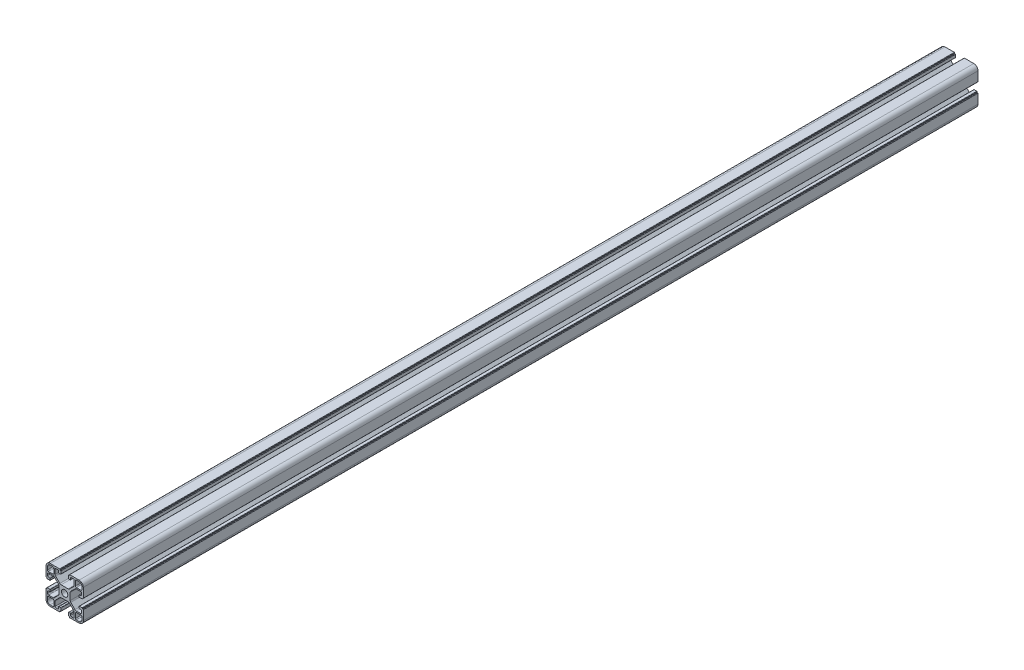
SolidWorks part; units mm, degrees
note: '?' marks a value the reader was unsure of.
material "6063-T5"
ref_plane "前视基准面" through (0, 0, 0) normal (0, 0, 1) x (1, 0, 0)
ref_plane "上视基准面" through (0, 0, 0) normal (0, 1, 0) x (1, 0, 0)
ref_plane "右视基准面" through (0, 0, 0) normal (1, 0, 0) x (0, 0, -1)
sketch "草图1" plane through (0, 0, 0) normal (0, 0, 1) x (1, 0, 0)
  line L0 (5.1, -19.2) -> (5.1, -19.7)
  line L1 (4.4, -19) -> (4.9, -19)
  line L2 (5.4, -20) -> (15.5, -20)
  line L3 (4.1, -15.8) -> (4.1, -18.8)
  line L4 (20, -15.5) -> (20, -5.4)
  line L5 (6.1, -15.5) -> (4.4, -15.5)
  line L6 (19.7, -5.1) -> (19.2, -5.1)
  line L7 (6.4, -17.2) -> (6.4, -15.8)
  line L8 (19, -4.9) -> (19, -4.4)
  line L9 (9.25, -18.2) -> (7.4, -18.2)
  line L10 (18.7, -4.1) -> (15.8, -4.1)
  line L11 (10.25, -12.4926) -> (10.25, -17.2)
  line L12 (15.5, -4.4) -> (15.5, -6.1)
  line L13 (5.1716, -6.5858) -> (9.6642, -11.0784)
  line L14 (15.8, -6.4) -> (17.2, -6.4)
  line L15 (-3.7574, -6) -> (3.7574, -6)
  line L16 (18.2, -7.4) -> (18.2, -9.25)
  line L17 (-9.6642, -11.0784) -> (-5.1716, -6.5858)
  line L18 (17.2, -10.25) -> (12.4926, -10.25)
  line L19 (-10.25, -17.2) -> (-10.25, -12.4926)
  line L20 (11.0784, -9.6642) -> (6.5858, -5.1716)
  line L21 (-7.4, -18.2) -> (-9.25, -18.2)
  line L22 (6, -3.7574) -> (6, 3.7574)
  line L23 (-6.4, -15.8) -> (-6.4, -17.2)
  line L24 (6.5858, 5.1716) -> (11.0784, 9.6642)
  line L25 (-4.4, -15.5) -> (-6.1, -15.5)
  line L26 (12.4926, 10.25) -> (17.2, 10.25)
  line L27 (-4.1, -18.8) -> (-4.1, -15.8)
  line L28 (18.2, 9.25) -> (18.2, 7.4)
  line L29 (-4.9, -19) -> (-4.4, -19)
  line L30 (17.2, 6.4) -> (15.8, 6.4)
  line L31 (-5.1, -19.7) -> (-5.1, -19.2)
  line L32 (15.5, 6.1) -> (15.5, 4.4)
  line L33 (-15.5, -20) -> (-5.4, -20)
  line L34 (15.8, 4.1) -> (18.7, 4.1)
  line L35 (-20, -5.4) -> (-20, -15.5)
  line L36 (19, 4.4) -> (19, 4.9)
  line L37 (-19.2, -5.1) -> (-19.7, -5.1)
  line L38 (19.2, 5.1) -> (19.7, 5.1)
  line L39 (-19, -4.4) -> (-19, -4.9)
  line L40 (20, 5.4) -> (20, 15.5)
  line L41 (-15.8, -4.1) -> (-18.7, -4.1)
  line L42 (15.5, 20) -> (5.4, 20)
  line L43 (-15.5, -6.1) -> (-15.5, -4.4)
  line L44 (5.1, 19.7) -> (5.1, 19.2)
  line L45 (-17.2, -6.4) -> (-15.8, -6.4)
  line L46 (4.9, 19) -> (4.4, 19)
  line L47 (-18.2, -9.25) -> (-18.2, -7.4)
  line L48 (4.1, 18.7) -> (4.1, 15.8)
  line L49 (-12.4926, -10.25) -> (-17.2, -10.25)
  line L50 (4.4, 15.5) -> (6.1, 15.5)
  line L51 (-6.5858, -5.1716) -> (-11.0784, -9.6642)
  line L52 (6.4, 15.8) -> (6.4, 17.2)
  line L53 (-6, 3.7574) -> (-6, -3.7574)
  line L54 (7.4, 18.2) -> (9.25, 18.2)
  line L55 (-11.0784, 9.6642) -> (-6.5858, 5.1716)
  line L56 (10.25, 17.2) -> (10.25, 12.4926)
  line L57 (-17.2, 10.25) -> (-12.4926, 10.25)
  line L58 (9.6642, 11.0784) -> (5.1716, 6.5858)
  line L59 (-18.2, 7.4) -> (-18.2, 9.25)
  line L60 (3.7574, 6) -> (-3.7574, 6)
  line L61 (-15.8, 6.4) -> (-17.2, 6.4)
  line L62 (-5.1716, 6.5858) -> (-9.6642, 11.0784)
  line L63 (-15.5, 4.4) -> (-15.5, 6.1)
  line L64 (-10.25, 12.4926) -> (-10.25, 17.2)
  line L65 (-18.7, 4.1) -> (-15.8, 4.1)
  line L66 (-9.25, 18.2) -> (-7.4, 18.2)
  line L67 (-19, 4.9) -> (-19, 4.4)
  line L68 (-6.4, 17.2) -> (-6.4, 15.8)
  line L69 (-19.7, 5.1) -> (-19.2, 5.1)
  line L70 (-6.1, 15.5) -> (-4.4, 15.5)
  line L71 (-20, 15.5) -> (-20, 5.4)
  line L72 (-4.1, 15.8) -> (-4.1, 18.7)
  line L73 (-5.4, 20) -> (-15.5, 20)
  line L74 (-4.4, 19) -> (-4.9, 19)
  line L75 (-5.1, 19.2) -> (-5.1, 19.7)
  line L76 (12.55, 18.5) -> (15.5, 18.5)
  line L77 (11.55, 12.55) -> (11.55, 17.5)
  line L78 (18.5, 15.5) -> (18.5, 12.55)
  line L79 (17.5, 11.55) -> (12.55, 11.55)
  line L80 (-11.55, 17.5) -> (-11.55, 12.55)
  line L81 (-15.5, 18.5) -> (-12.55, 18.5)
  line L82 (-12.55, 11.55) -> (-17.5, 11.55)
  line L83 (-18.5, 12.55) -> (-18.5, 15.5)
  line L84 (-12.55, -18.5) -> (-15.5, -18.5)
  line L85 (-11.55, -12.55) -> (-11.55, -17.5)
  line L86 (-18.5, -15.5) -> (-18.5, -12.55)
  line L87 (-17.5, -11.55) -> (-12.55, -11.55)
  line L88 (11.55, -17.5) -> (11.55, -12.55)
  line L89 (15.5, -18.5) -> (12.55, -18.5)
  line L90 (12.55, -11.55) -> (17.5, -11.55)
  line L91 (18.5, -12.55) -> (18.5, -15.5)
  arc A0 (5.1, -19.2) -> (4.9, -19) centre (4.9, -19.2) ccw
  arc A1 (5.1, -19.7) -> (5.4, -20) centre (5.4, -19.7) ccw
  arc A2 (4.1, -18.8) -> (4.4, -19) centre (4.3282, -18.7827) ccw
  arc A3 (15.5, -20) -> (20, -15.5) centre (15.5, -15.5) ccw
  arc A4 (4.4, -15.5) -> (4.1, -15.8) centre (4.4, -15.8) ccw
  arc A5 (20, -5.4) -> (19.7, -5.1) centre (19.7, -5.4) ccw
  arc A6 (6.4, -15.8) -> (6.1, -15.5) centre (6.1, -15.8) ccw
  arc A7 (19, -4.9) -> (19.2, -5.1) centre (19.2, -4.9) ccw
  arc A8 (6.4, -17.2) -> (7.4, -18.2) centre (7.4, -17.2) ccw
  arc A9 (19, -4.4) -> (18.7, -4.1) centre (18.7, -4.4) ccw
  arc A10 (9.25, -18.2) -> (10.25, -17.2) centre (9.25, -17.2) ccw
  arc A11 (15.8, -4.1) -> (15.5, -4.4) centre (15.8, -4.4) ccw
  arc A12 (10.25, -12.4926) -> (9.6642, -11.0784) centre (8.25, -12.4926) ccw
  arc A13 (15.5, -6.1) -> (15.8, -6.4) centre (15.8, -6.1) ccw
  arc A14 (5.1716, -6.5858) -> (3.7574, -6) centre (3.7574, -8) ccw
  arc A15 (18.2, -7.4) -> (17.2, -6.4) centre (17.2, -7.4) ccw
  arc A16 (-3.7574, -6) -> (-5.1716, -6.5858) centre (-3.7574, -8) ccw
  arc A17 (17.2, -10.25) -> (18.2, -9.25) centre (17.2, -9.25) ccw
  arc A18 (-9.6642, -11.0784) -> (-10.25, -12.4926) centre (-8.25, -12.4926) ccw
  arc A19 (11.0784, -9.6642) -> (12.4926, -10.25) centre (12.4926, -8.25) ccw
  arc A20 (-10.25, -17.2) -> (-9.25, -18.2) centre (-9.25, -17.2) ccw
  arc A21 (6, -3.7574) -> (6.5858, -5.1716) centre (8, -3.7574) ccw
  arc A22 (-7.4, -18.2) -> (-6.4, -17.2) centre (-7.4, -17.2) ccw
  arc A23 (6.5858, 5.1716) -> (6, 3.7574) centre (8, 3.7574) ccw
  arc A24 (-6.1, -15.5) -> (-6.4, -15.8) centre (-6.1, -15.8) ccw
  arc A25 (12.4926, 10.25) -> (11.0784, 9.6642) centre (12.4926, 8.25) ccw
  arc A26 (-4.1, -15.8) -> (-4.4, -15.5) centre (-4.4, -15.8) ccw
  arc A27 (18.2, 9.25) -> (17.2, 10.25) centre (17.2, 9.25) ccw
  arc A28 (-4.4, -19) -> (-4.1, -18.8) centre (-4.3282, -18.7827) ccw
  arc A29 (17.2, 6.4) -> (18.2, 7.4) centre (17.2, 7.4) ccw
  arc A30 (-4.9, -19) -> (-5.1, -19.2) centre (-4.9, -19.2) ccw
  arc A31 (15.8, 6.4) -> (15.5, 6.1) centre (15.8, 6.1) ccw
  arc A32 (-5.4, -20) -> (-5.1, -19.7) centre (-5.4, -19.7) ccw
  arc A33 (15.5, 4.4) -> (15.8, 4.1) centre (15.8, 4.4) ccw
  arc A34 (-20, -15.5) -> (-15.5, -20) centre (-15.5, -15.5) ccw
  arc A35 (18.7, 4.1) -> (19, 4.4) centre (18.7, 4.4) ccw
  arc A36 (-19.7, -5.1) -> (-20, -5.4) centre (-19.7, -5.4) ccw
  arc A37 (19.2, 5.1) -> (19, 4.9) centre (19.2, 4.9) ccw
  arc A38 (-19.2, -5.1) -> (-19, -4.9) centre (-19.2, -4.9) ccw
  arc A39 (19.7, 5.1) -> (20, 5.4) centre (19.7, 5.4) ccw
  arc A40 (-18.7, -4.1) -> (-19, -4.4) centre (-18.7, -4.4) ccw
  arc A41 (20, 15.5) -> (15.5, 20) centre (15.5, 15.5) ccw
  arc A42 (-15.5, -4.4) -> (-15.8, -4.1) centre (-15.8, -4.4) ccw
  arc A43 (5.4, 20) -> (5.1, 19.7) centre (5.4, 19.7) ccw
  arc A44 (-15.8, -6.4) -> (-15.5, -6.1) centre (-15.8, -6.1) ccw
  arc A45 (4.9, 19) -> (5.1, 19.2) centre (4.9, 19.2) ccw
  arc A46 (-17.2, -6.4) -> (-18.2, -7.4) centre (-17.2, -7.4) ccw
  arc A47 (4.4, 19) -> (4.1, 18.7) centre (4.4, 18.7) ccw
  arc A48 (-18.2, -9.25) -> (-17.2, -10.25) centre (-17.2, -9.25) ccw
  arc A49 (4.1, 15.8) -> (4.4, 15.5) centre (4.4, 15.8) ccw
  arc A50 (-12.4926, -10.25) -> (-11.0784, -9.6642) centre (-12.4926, -8.25) ccw
  arc A51 (6.1, 15.5) -> (6.4, 15.8) centre (6.1, 15.8) ccw
  arc A52 (-6.5858, -5.1716) -> (-6, -3.7574) centre (-8, -3.7574) ccw
  arc A53 (7.4, 18.2) -> (6.4, 17.2) centre (7.4, 17.2) ccw
  arc A54 (-6, 3.7574) -> (-6.5858, 5.1716) centre (-8, 3.7574) ccw
  arc A55 (10.25, 17.2) -> (9.25, 18.2) centre (9.25, 17.2) ccw
  arc A56 (-11.0784, 9.6642) -> (-12.4926, 10.25) centre (-12.4926, 8.25) ccw
  arc A57 (9.6642, 11.0784) -> (10.25, 12.4926) centre (8.25, 12.4926) ccw
  arc A58 (-17.2, 10.25) -> (-18.2, 9.25) centre (-17.2, 9.25) ccw
  arc A59 (3.7574, 6) -> (5.1716, 6.5858) centre (3.7574, 8) ccw
  arc A60 (-18.2, 7.4) -> (-17.2, 6.4) centre (-17.2, 7.4) ccw
  arc A61 (-5.1716, 6.5858) -> (-3.7574, 6) centre (-3.7574, 8) ccw
  arc A62 (-15.5, 6.1) -> (-15.8, 6.4) centre (-15.8, 6.1) ccw
  arc A63 (-10.25, 12.4926) -> (-9.6642, 11.0784) centre (-8.25, 12.4926) ccw
  arc A64 (-15.8, 4.1) -> (-15.5, 4.4) centre (-15.8, 4.4) ccw
  arc A65 (-9.25, 18.2) -> (-10.25, 17.2) centre (-9.25, 17.2) ccw
  arc A66 (-19, 4.4) -> (-18.7, 4.1) centre (-18.7, 4.4) ccw
  arc A67 (-6.4, 17.2) -> (-7.4, 18.2) centre (-7.4, 17.2) ccw
  arc A68 (-19, 4.9) -> (-19.2, 5.1) centre (-19.2, 4.9) ccw
  arc A69 (-6.4, 15.8) -> (-6.1, 15.5) centre (-6.1, 15.8) ccw
  arc A70 (-20, 5.4) -> (-19.7, 5.1) centre (-19.7, 5.4) ccw
  arc A71 (-4.4, 15.5) -> (-4.1, 15.8) centre (-4.4, 15.8) ccw
  arc A72 (-15.5, 20) -> (-20, 15.5) centre (-15.5, 15.5) ccw
  arc A73 (-4.1, 18.7) -> (-4.4, 19) centre (-4.4, 18.7) ccw
  arc A74 (-5.1, 19.7) -> (-5.4, 20) centre (-5.4, 19.7) ccw
  arc A75 (-5.1, 19.2) -> (-4.9, 19) centre (-4.9, 19.2) ccw
  arc A76 (12.55, 18.5) -> (11.55, 17.5) centre (12.55, 17.5) ccw
  arc A77 (18.5, 15.5) -> (15.5, 18.5) centre (15.5, 15.5) ccw
  arc A78 (11.55, 12.55) -> (12.55, 11.55) centre (12.55, 12.55) ccw
  arc A79 (17.5, 11.55) -> (18.5, 12.55) centre (17.5, 12.55) ccw
  arc A80 (-11.55, 17.5) -> (-12.55, 18.5) centre (-12.55, 17.5) ccw
  arc A81 (-12.55, 11.55) -> (-11.55, 12.55) centre (-12.55, 12.55) ccw
  arc A82 (-15.5, 18.5) -> (-18.5, 15.5) centre (-15.5, 15.5) ccw
  arc A83 (-18.5, 12.55) -> (-17.5, 11.55) centre (-17.5, 12.55) ccw
  circle A84 centre (0, 0) radius 3.4
  arc A85 (-12.55, -18.5) -> (-11.55, -17.5) centre (-12.55, -17.5) ccw
  arc A86 (-18.5, -15.5) -> (-15.5, -18.5) centre (-15.5, -15.5) ccw
  arc A87 (-11.55, -12.55) -> (-12.55, -11.55) centre (-12.55, -12.55) ccw
  arc A88 (-17.5, -11.55) -> (-18.5, -12.55) centre (-17.5, -12.55) ccw
  arc A89 (11.55, -17.5) -> (12.55, -18.5) centre (12.55, -17.5) ccw
  arc A90 (12.55, -11.55) -> (11.55, -12.55) centre (12.55, -12.55) ccw
  arc A91 (15.5, -18.5) -> (18.5, -15.5) centre (15.5, -15.5) ccw
  arc A92 (18.5, -12.55) -> (17.5, -11.55) centre (17.5, -12.55) ccw
extrude "凸台-拉伸1" add sketch "草图1" along normal blind 960
ref_axis "基准轴" through (0, 0, 0) along (0, 0, 1)?
ref_plane "基准面" through (0, 0, -20) normal (0, 0, -1) x (-1, 0, 0)
hole_wizard "螺纹孔E" [suppressed] positions "草图3" profile "草图2" tap size "M8" standard "GB"
sketch "草图3" plane through (0, 0, 300) normal (0, 0, 1) x (1, 0, 0)
  point P0 (0, 0)
sketch "草图2" plane through (0, 0, 300) normal (1, 0, 0) x (0, -1, 0)
  line L0 (0, 0) -> (0, 28.2959)
  line L1 (0, 28.2959) -> (3.405, 26.25)
  line L2 (3.405, 26.25) -> (3.405, 0)
  line L5 (3.405, 0) -> (0, 0)
  line L10 (0, 28.2959) -> (-3.405, 26.25) construction
  line L11 (0, -6.35) -> (0, 107.95) construction
  dimension "螺纹孔钻头直径" = 6.81
  dimension "螺纹孔钻头深度" = 26.25
  dimension "导头角度" = 118
cosmetic thread "孔螺蚊线1" [suppressed] parameters "D1"=20, "D2"=8
hole_wizard "螺纹孔S" [suppressed] positions "草图5" profile "草图4" tap size "M8" standard "GB"
sketch "草图5" plane through (0, 0, 0) normal (0, 0, -1) x (-1, 0, 0)
  point P0 (0, 0)
sketch "草图4" plane through (0, 0, 0) normal (1, 0, 0) x (0, 1, 0)
  line L0 (0, 0) -> (0, 28.2959)
  line L1 (0, 28.2959) -> (3.405, 26.25)
  line L2 (3.405, 26.25) -> (3.405, 0)
  line L5 (3.405, 0) -> (0, 0)
  line L10 (0, 28.2959) -> (-3.405, 26.25) construction
  line L11 (0, -6.35) -> (0, 107.95) construction
  dimension "螺纹孔钻头直径" = 6.81
  dimension "螺纹孔钻头深度" = 26.25
  dimension "导头角度" = 118
cosmetic thread "孔螺蚊线2" [suppressed] parameters "D1"=20, "D2"=8
other "内孔SA1" [suppressed] parameters "D1"=16.8
sketch "草图6" plane through (0, 20, 0) normal (0, 1, 0) x (1, 0, 0)
  line L0 (-5.4, 0) -> (-15.5, 0) construction
  line L1 (0, -22) -> (0, 22) construction
  circle A0 centre (0, -19) radius 10
  dimension "D1" = 20
  dimension "D2" = 19
other "内孔EA1" [suppressed] parameters "D1"=16.8
sketch "草图7" plane through (0, 20, 0) normal (0, 1, 0) x (1, 0, 0)
  line L0 (-5.4, -300) -> (-15.5, -300) construction
  line L1 (0, -22) -> (0, 22) construction
  circle A0 centre (0, -281) radius 10
  dimension "D1" = 20
  dimension "D2" = 19
other "内孔SB1" [suppressed] parameters "D1"=16.8
sketch "草图8" plane through (-20, 0, 0) normal (-1, 0, 0) x (0, 0, 1)
  line L0 (0, -5.4) -> (0, -15.5) construction
  line L1 (22, 0) -> (-22, 0) construction
  circle A0 centre (19, 0) radius 10
  dimension "D1" = 20
  dimension "D2" = 19
other "内孔EB1" [suppressed] parameters "D1"=16.8
sketch "草图9" plane through (-20, 0, 0) normal (-1, 0, 0) x (0, 0, 1)
  line L0 (300, -5.4) -> (300, -15.5) construction
  line L1 (22, 0) -> (-22, 0) construction
  circle A0 centre (281, 0) radius 10
  dimension "D1" = 20
  dimension "D2" = 19
other "内孔SC1" [suppressed] parameters "D1"=16.8
sketch "草图10" plane through (0, -20, 0) normal (0, -1, 0) x (-1, 0, 0)
  line L0 (-5.4, 0) -> (-15.5, 0) construction
  line L1 (0, 22) -> (0, -22) construction
  circle A0 centre (0, -19) radius 10
  dimension "D1" = 20
  dimension "D2" = 19
other "内孔EC1" [suppressed] parameters "D1"=16.8
sketch "草图11" plane through (0, -20, 0) normal (0, -1, 0) x (-1, 0, 0)
  line L0 (-5.4, -300) -> (-15.5, -300) construction
  line L1 (0, 22) -> (0, -22) construction
  circle A0 centre (0, -281) radius 10
  dimension "D1" = 20
  dimension "D2" = 19
other "内孔SD1" [suppressed] parameters "D1"=16.8
sketch "草图12" plane through (20, 0, 0) normal (1, 0, 0) x (0, 0, -1)
  line L0 (0, 5.4) -> (0, 15.5) construction
  line L1 (22, 0) -> (-22, 0) construction
  circle A0 centre (-19, 0) radius 10
  dimension "D1" = 20
  dimension "D2" = 19
other "内孔ED1" [suppressed] parameters "D1"=16.8
sketch "草图13" plane through (20, 0, 0) normal (1, 0, 0) x (0, 0, -1)
  line L0 (-300, 5.4) -> (-300, 15.5) construction
  line L1 (22, 0) -> (-22, 0) construction
  circle A0 centre (-281, 0) radius 10
  dimension "D1" = 20
  dimension "D2" = 19
other "锚孔SA1" [suppressed] parameters "D1"=40
sketch "草图14" plane through (0, 20, 0) normal (0, 1, 0) x (1, 0, 0)
  line L0 (-5.4, 0) -> (-15.5, 0) construction
  line L1 (0, -22) -> (0, 22) construction
  circle A0 centre (0, -18) radius 5.5
  dimension "D1" = 11
  dimension "D2" = 18
other "锚孔EA1" [suppressed] parameters "D1"=40
sketch "草图15" plane through (0, 20, 0) normal (0, 1, 0) x (1, 0, 0)
  line L0 (-5.4, -300) -> (-15.5, -300) construction
  line L1 (0, -22) -> (0, 22) construction
  circle A0 centre (0, -282) radius 5.5
  dimension "D1" = 11
  dimension "D2" = 18
other "锚孔SB1" [suppressed] parameters "D1"=40
sketch "草图16" plane through (-20, 0, 0) normal (-1, 0, 0) x (0, 0, 1)
  line L0 (0, -5.4) -> (0, -15.5) construction
  line L1 (22, 0) -> (-22, 0) construction
  circle A0 centre (18, 0) radius 5.5
  dimension "D1" = 11
  dimension "D2" = 18
other "锚孔EB1" [suppressed] parameters "D1"=40
sketch "草图17" plane through (-20, 0, 0) normal (-1, 0, 0) x (0, 0, 1)
  line L0 (300, -5.4) -> (300, -15.5) construction
  line L1 (22, 0) -> (-22, 0) construction
  circle A0 centre (282, 0) radius 5.5
  dimension "D1" = 11
  dimension "D2" = 18
other "锚孔SC1" [suppressed] parameters "D1"=40.1
sketch "草图18" plane through (0, -20, 0) normal (0, -1, 0) x (-1, 0, 0)
  line L0 (-5.4, 0) -> (-15.5, 0) construction
  line L1 (0, 22) -> (0, -22) construction
  circle A0 centre (0, -18) radius 5.5
  dimension "D1" = 11
  dimension "D2" = 18
other "锚孔EC1" [suppressed] parameters "D1"=40.1
sketch "草图19" plane through (0, -20, 0) normal (0, -1, 0) x (-1, 0, 0)
  line L0 (-5.4, -300) -> (-15.5, -300) construction
  line L1 (0, 22) -> (0, -22) construction
  circle A0 centre (0, -282) radius 5.5
  dimension "D1" = 11
  dimension "D2" = 18
other "锚孔SD1" [suppressed] parameters "D1"=40.1
sketch "草图20" plane through (20, 0, 0) normal (1, 0, 0) x (0, 0, -1)
  line L0 (0, 5.4) -> (0, 15.5) construction
  line L1 (22, 0) -> (-22, 0) construction
  circle A0 centre (-18, 0) radius 5.5
  dimension "D1" = 11
  dimension "D2" = 18
other "锚孔ED1" [suppressed] parameters "D1"=40.1
sketch "草图21" plane through (20, 0, 0) normal (1, 0, 0) x (0, 0, -1)
  line L0 (-300, 5.4) -> (-300, 15.5) construction
  line L1 (22, 0) -> (-22, 0) construction
  circle A0 centre (-282, 0) radius 5.5
  dimension "D1" = 11
  dimension "D2" = 18
